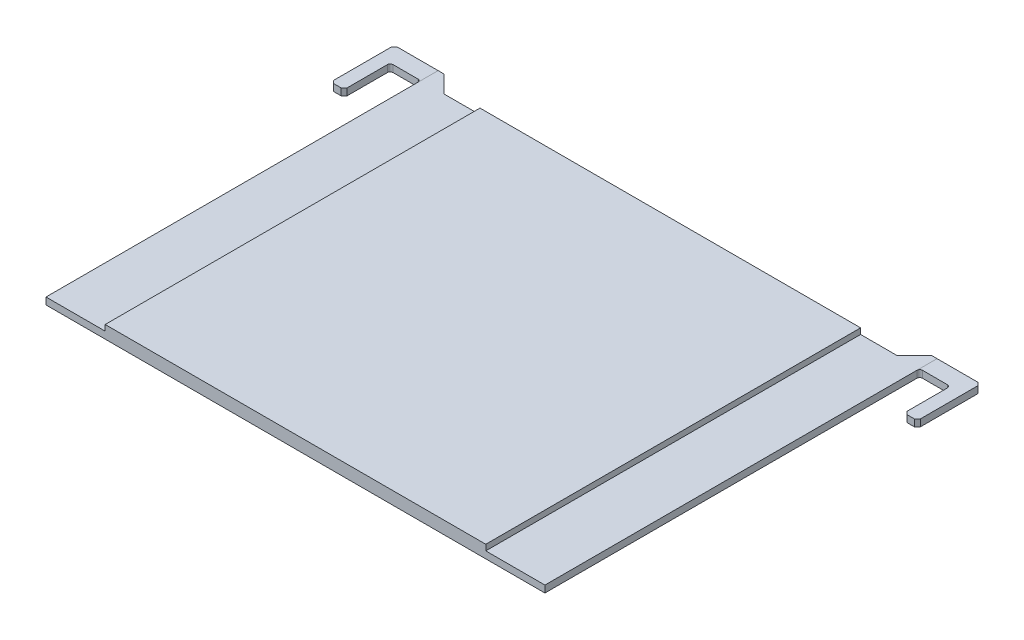
SolidWorks part; units mm, degrees
ref_plane "Front Plane" through (0, 0, 0) normal (0, 0, 1) x (1, 0, 0)
ref_plane "Top Plane" through (0, 0, 0) normal (0, 1, 0) x (1, 0, 0)
ref_plane "Right Plane" through (0, 0, 0) normal (1, 0, 0) x (0, 0, -1)
sketch "Sketch1" plane through (0, 0, 0) normal (0, 1, 0) x (1, 0, 0)
  line L1 (-43.26, -32.5) -> (43.26, -32.5)
  line L2 (-43.26, -32.5) -> (-43.26, 32.5)
  line L3 (-43.26, 32.5) -> (43.26, 32.5)
  line L4 (43.26, -32.5) -> (43.26, 32.5)
  line L5 (-43.26, -32.5) -> (43.26, 32.5) construction
  line L6 (-43.26, 32.5) -> (43.26, -32.5) construction
  point P0 (0, 0)
  dimension "D1" = 86.52
  dimension "D2" = 65
extrude "Boss-Extrude1" add sketch "Sketch1" along normal blind 1.2
sketch "Sketch2" plane through (0, 0, 32.5) normal (0, 0, 1) x (1, 0, 0)
  line L0 (-43.26, 1.2) -> (43.26, 1.2) construction
  line L1 (-33, 1.2) -> (33, 1.2)
  line L2 (-33, 1.2) -> (-33, 2.2)
  line L3 (-33, 2.2) -> (33, 2.2)
  line L4 (33, 1.2) -> (33, 2.2)
  line L5 (-33, 1.2) -> (33, 2.2) construction
  line L6 (-33, 2.2) -> (33, 1.2) construction
  point P4 (0, 1.7)
  point P7 (0, 0)
  dimension "D1" = 66
  dimension "D2" = 1
extrude "Boss-Extrude2" add sketch "Sketch2" against normal up to surface (65 mm away) up to face at (0, 0.6, -32.5)
sketch "Sketch3" plane through (0, 0, -32.5) normal (0, 0, -1) x (-1, 0, 0)
  line L0 (43.26, 0) -> (46.0396, -2.1197) construction
  line L1 (46.0396, -2.1197) -> (50.8591, -2.1197) construction
  line L2 (43.26, 1.2) -> (45.8591, -0.782) construction
  line L3 (45.8591, -0.782) -> (50.8591, -0.782) construction
  line L4 (50.8591, -0.782) -> (50.8591, -2.1197) construction
  line L5 (50.3144, -33.8) -> (45.8591, -0.782) construction
  line L6 (43.2588, 1.2) -> (45.6144, -0.5955) construction
  line L7 (43.2588, 1.2) -> (45.6144, -0.5955) construction
  line L8 (48.1144, 1.2) -> (52.2322, -29.318) construction
  line L9 (48.3818, -0.782) -> (48.5623, -2.1197) construction
  line L10 (48.58, -0.7553) -> (48.7605, -2.0929) construction
  line L11 (0, 2.2) -> (0, 0) construction
  line L12 (-48.3818, -0.782) -> (-48.5623, -2.1197) construction
  line L13 (-43.26, 0) -> (43.26, 0)
  line L14 (43.26, 0) -> (43.26, 1.2)
  line L15 (43.26, 1.2) -> (33, 1.2)
  line L16 (33, 1.2) -> (33, 2.2)
  line L17 (33, 2.2) -> (-33, 2.2)
  line L18 (-33, 2.2) -> (-33, 1.2)
  line L19 (-33, 1.2) -> (-43.26, 1.2)
  line L20 (-43.26, 1.2) -> (-43.26, 0)
  line L21 (-43.26, 0) -> (-40.26, 0)
  line L22 (43.26, 1.1991) -> (43.26, 1.2)
  line L23 (43.26, 1.2) -> (33, 1.2)
  line L24 (33, 1.2) -> (33, 2.2)
  line L25 (33, 2.2) -> (0, 2.2)
  line L27 (-40.26, 1.2) -> (-43.26, 1.2)
  line L28 (-43.26, 1.2) -> (-43.26, 1.1991)
  line L29 (-43.26, 1.2) -> (-33, 1.2)
  line L30 (-43.26, 1.1991) -> (-43.26, 1.2)
  line L31 (-48.58, -0.7553) -> (-48.7605, -2.0929) construction
  line L32 (-43.2588, 1.2) -> (-45.6144, -0.5955) construction
  line L33 (-50.8591, -0.782) -> (-50.8591, -2.1197) construction
  line L34 (-45.8591, -0.782) -> (-50.8591, -0.782) construction
  line L35 (-43.26, 1.2) -> (-45.8591, -0.782)
  line L36 (-46.0396, -2.1197) -> (-50.8591, -2.1197) construction
  line L37 (-43.26, 0) -> (-46.0396, -2.1197) construction
  line L38 (-43.2588, 1.2) -> (-40.26, 1.2)
  line L39 (-40.26, 1.2) -> (-40.26, 0)
  line L40 (-40.26, 0) -> (-43.26, 0)
  line L41 (0, 0) -> (43.26, 0)
  line L42 (43.26, 1.1991) -> (50.8591, 1.1991)
  line L43 (43.26, 1.2) -> (40.26, 1.2)
  line L44 (43.26, 1.2) -> (43.26, 0)
  line L45 (43.26, 0) -> (40.26, 0)
  line L46 (40.26, 1.2) -> (40.26, 0)
  line L47 (43.26, 1.2) -> (40.26, 0) construction
  line L48 (43.26, 0) -> (40.26, 1.2) construction
  line L49 (50.8591, 1.1991) -> (50.8591, 0)
  line L50 (50.8591, 0) -> (43.26, 0)
  line L51 (-43.2588, 1.2) -> (-45.6144, -0.5955) construction
  line L52 (-43.26, 1.2) -> (-45.8591, -0.782) construction
  line L53 (-50.8591, 0) -> (-43.26, 0)
  line L54 (-50.8591, 1.1991) -> (-50.8591, 0)
  line L55 (-43.26, 1.1991) -> (-50.8591, 1.1991)
  point P43 (41.76, 0.6)
  dimension "D2" = 5
  dimension "D3" = 0.2
  dimension "D4" = 3
  dimension "D5" = 43.26
  dimension "D6" = 3
  dimension "D1" = 0
extrude "Boss-Extrude5" add sketch "Sketch3" along normal blind 3 and the other way blind 0.01
chamfer "Chamfer1" distance 2 angle 45 1 edges at (40.26, 0.6, -35.5)
chamfer "Chamfer2" distance 2 angle 45 1 edges at (-40.26, 0.6, -35.5)
chamfer "Chamfer3" distance 1 angle 45 2 edges at (-40.26, 0.6, -32.5) (40.26, 0.6, -32.5)
sketch "Sketch5" plane through (0, 0, -32.49) normal (0, 0, 1) x (1, 0, 0)
  line L0 (-50.8591, 0) -> (-43.26, 0) construction
  line L1 (-50.8591, 1.1991) -> (-48.5591, 1.1991)
  line L2 (-50.8591, 1.1991) -> (-50.8591, 0)
  line L3 (-50.8591, 0) -> (-48.5591, 0)
  line L4 (-48.5591, 1.1991) -> (-48.5591, 0)
  line L5 (-50.8591, 1.1991) -> (-48.5591, 0) construction
  line L6 (-50.8591, 0) -> (-48.5591, 1.1991) construction
  line L7 (0, 0) -> (0, 2.2)
  line L8 (-43.26, 0) -> (43.26, 0) construction
  line L9 (33, 2.2) -> (-33, 2.2) construction
  line L10 (50.8591, 0) -> (48.5591, 1.1991) construction
  line L11 (50.8591, 1.1991) -> (48.5591, 0) construction
  line L12 (48.5591, 1.1991) -> (48.5591, 0)
  line L13 (50.8591, 0) -> (48.5591, 0)
  line L14 (50.8591, 1.1991) -> (50.8591, 0)
  line L15 (50.8591, 1.1991) -> (48.5591, 1.1991)
  point P4 (-49.7091, 0.5995)
  point P18 (49.7091, 0.5995)
  line M3 (-50.8591, 0) -> (-43.26, 0)
  line M5 (-43.26, 1.1991) -> (-50.8591, 1.1991)
  line M6 (-50.8591, 1.1991) -> (-50.8591, 0)
  dimension "D1" = 2.3
extrude "Boss-Extrude7" add sketch "Sketch5" along normal blind 8 contours L4 M5 M6 M3 | L14 L15 L12 L13
chamfer "Chamfer5" distance 0.5 angle 45 6 edges at (-48.5591, 0.5995, -24.49) (-50.8591, 0.5995, -24.49) (-50.8591, 0.5995, -35.5) (50.8591, 0.5995, -35.5) (50.8591, 0.5995, -24.49) (48.5591, 0.5995, -24.49)
fillet "Fillet3" radius 0.5 4 edges at (48.5591, 0.5995, -32.49) (43.26, 0.5995, -32.49) (-48.5591, 0.5995, -32.49) (-43.26, 0.5995, -32.49)
